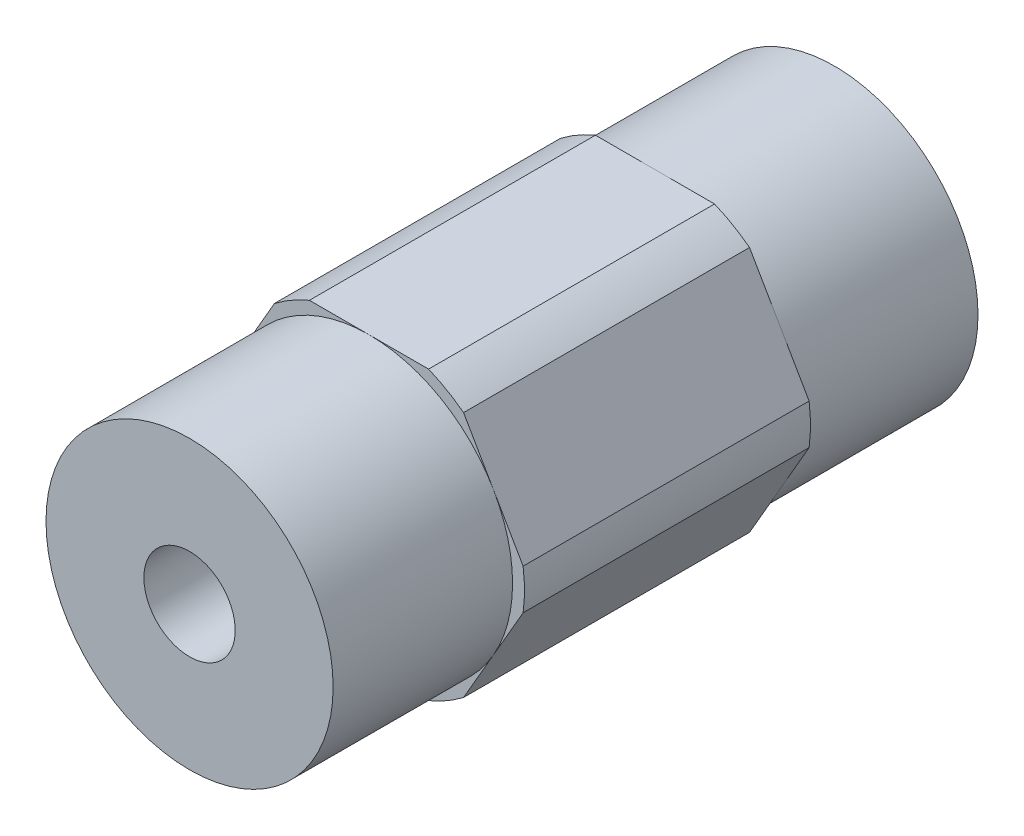
SolidWorks part; units mm, degrees
material "7075-T6 (SN)"
ref_plane "Front Plane" through (0, 0, 0) normal (0, 0, 1) x (1, 0, 0)
ref_plane "Top Plane" through (0, 0, 0) normal (0, 1, 0) x (1, 0, 0)
ref_plane "Right Plane" through (0, 0, 0) normal (1, 0, 0) x (0, 0, -1)
sketch "Sketch1" plane through (0, 0, 0) normal (0, 0, 1) x (1, 0, 0)
  line L1 (7.3323, 0) -> (3.6662, 6.35)
  line L2 (3.6662, 6.35) -> (-3.6662, 6.35)
  line L3 (-3.6662, 6.35) -> (-7.3323, 0)
  line L4 (-7.3323, 0) -> (-3.6662, -6.35)
  line L5 (-3.6662, -6.35) -> (3.6662, -6.35)
  line L6 (3.6662, -6.35) -> (7.3323, 0)
  circle A0 centre (0, 0) radius 6.35 construction
  circle A1 centre (0, 0) radius 2.0193
  circle A2 centre (0, 0) radius 6.875
  dimension "D1" = 12.7
  dimension "D2" = 4.0386
  dimension "D3" = 13.75
extrude "Boss-Extrude1" add sketch "Sketch1" along normal mid plane 28.5242 contours L1 A2 L2 L3 L4 L5 L6 A1 region at (6.6736, 0.4353, 0)
hole_wizard "#10-32 Tapped Hole1" positions "3DSketch1" profile "Sketch3" tap size "#10-32" standard "ANSI Inch"
sketch3d "3DSketch1"
  circle A0 centre (0, 0, -14.2621) radius 2.0193 construction
  circle A1 centre (0, 0, 14.2621) radius 2.0193 construction
  point P0 (0, 0, 14.2621)
  point P2 (0, 0, -14.2621)
  point P6 (0, 0, -12.2428)
  point P9 (0, 0, 16.2814)
sketch "Sketch3" plane through (0, 0, 14.2621) normal (1, 0, 0) x (0, -1, 0)
  line L0 (0, 0) -> (0, 13.1513)
  line L1 (0, 13.1513) -> (2.0193, 11.938)
  line L2 (2.0193, 11.938) -> (2.0193, 0)
  line L5 (2.0193, 0) -> (0, 0)
  line L10 (0, 13.1513) -> (-2.0193, 11.938) construction
  line L11 (0, -6.35) -> (0, 107.95) construction
  dimension "Tap Drill Dia." = 4.0386
  dimension "Tap Drill Depth" = 11.938
  dimension "Drill Angle" = 118
cosmetic thread "Hole Thread1" parameters "D1"=9.652, "D2"=4.826
cosmetic thread "Hole Thread2" parameters "D1"=9.652, "D2"=4.826
sketch "Sketch4" plane through (0, 0, 14.2621) normal (0, 0, 1) x (1, 0, 0)
  circle A0 centre (0, 0) radius 6.35
  dimension "D1" = 12.7
extrude "Cut-Extrude-Thin1" cut sketch "Sketch4" against normal blind 7.9375 thin thin type one direction wall 2.54
mirror "Mirror1" about plane through (0, 0, 0) normal (0, 0, 1) of "Cut-Extrude-Thin1"
equation "\"D3@Sketch1\"=13.75mm"
